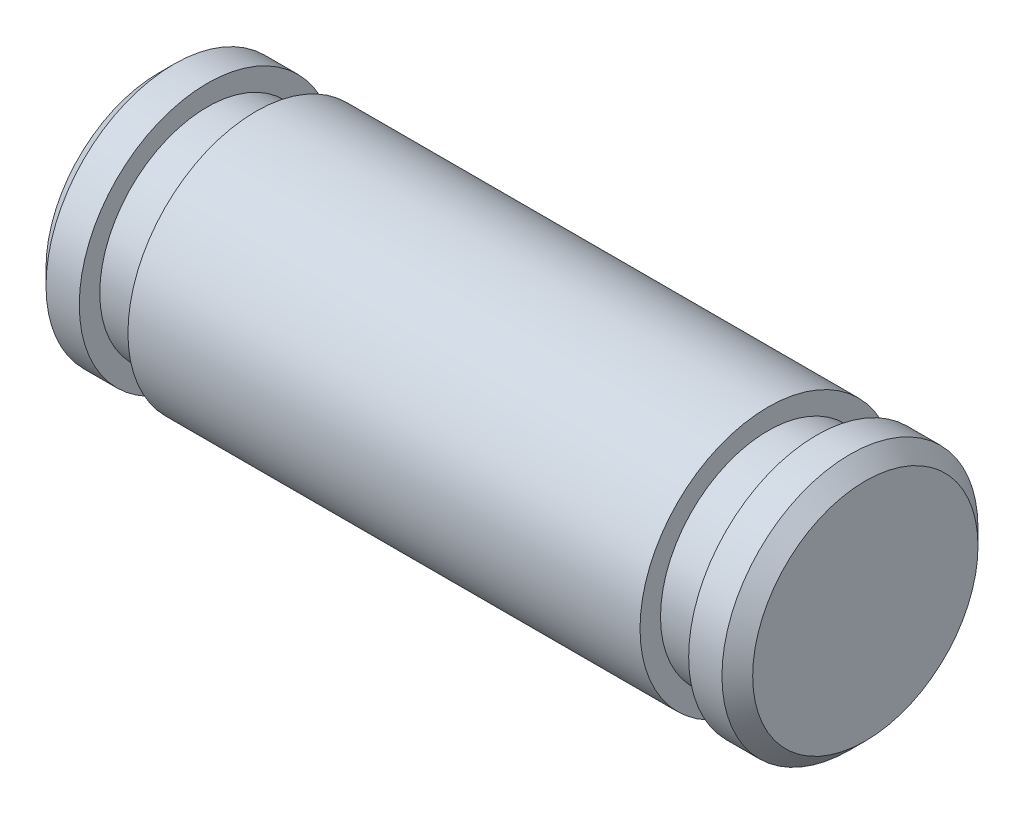
SolidWorks part; units mm, degrees
material "AISI 1045 Steel, cold drawn"
ref_plane "Front Plane" through (0, 0, 0) normal (0, 0, 1) x (1, 0, 0)
ref_plane "Top Plane" through (0, 0, 0) normal (0, 1, 0) x (1, 0, 0)
ref_plane "Right Plane" through (0, 0, 0) normal (1, 0, 0) x (0, 0, -1)
sketch "Sketch1" plane through (0, 0, 0) normal (0, 0, 1) x (1, 0, 0)
  line L0 (-8.763, 0) -> (-8.763, 2.794)
  line L1 (-8.763, 2.794) -> (-8.382, 3.175)
  line L2 (-8.382, 3.175) -> (-7.5565, 3.175)
  line L3 (-7.5565, 3.175) -> (-7.5565, 2.667)
  line L4 (-7.5565, 2.667) -> (-6.35, 2.667)
  line L5 (-6.35, 2.667) -> (-6.35, 3.175)
  line L6 (-6.35, 3.175) -> (6.35, 3.175)
  line L7 (6.35, 3.175) -> (6.35, 2.667)
  line L8 (6.35, 2.667) -> (7.5565, 2.667)
  line L9 (7.5565, 2.667) -> (7.5565, 3.175)
  line L10 (7.5565, 3.175) -> (8.382, 3.175)
  line L11 (8.382, 3.175) -> (8.763, 2.794)
  line L12 (8.763, 2.794) -> (8.763, 0)
  line L13 (8.763, 0) -> (-8.763, 0)
  line L14 (8.763, 0) -> (-8.763, 0) construction
revolve "Revolve1" add sketch "Sketch1" angle 360 about L14 reverse direction yes
ref_plane "Plane1" through (6.9533, 0, 0) normal (1, 0, 0) x (0, 0, -1)
ref_plane "Plane2" through (-6.9533, 0, 0) normal (1, 0, 0) x (0, 0, -1)
ref_plane "p1 XY" through (0, 0, 0) normal (1, 0, 0) x (0, 0, -1)
ref_plane "p1 XZ" through (0, 0, 0) normal (0, -1, 0) x (-1, 0, 0)
ref_plane "p1 YZ" through (0, 0, 3.175) normal (0, 0, -1) x (-1, 0, 0)
ref_axis "p1 X" through (0, 0, 80.9) along (0, 0, -1)
ref_axis "p1 Y" through (0, -50, 3.175) along (0, 1, 0)
ref_axis "p1 Z" through (80.9, 0, 3.175) along (-1, 0, 0)
sketch3d "p1"
  point P0 (0, 0, 3.175)
ref_plane "p2 XY" through (0, 0, 0) normal (1, 0, 0) x (0, 0, -1)
ref_plane "p2 XZ" through (0, 0, 0) normal (0, -1, 0) x (-1, 0, 0)
ref_plane "p2 YZ" through (0, 0, -3.175) normal (0, 0, -1) x (-1, 0, 0)
ref_axis "p2 X" through (0, 0, 80.9) along (0, 0, -1)
ref_axis "p2 Y" through (0, -50, -3.175) along (0, 1, 0)
ref_axis "p2 Z" through (80.9, 0, -3.175) along (-1, 0, 0)
sketch3d "p2"
  point P0 (0, 0, -3.175)
ref_plane "pin XY" through (0, 0, 0) normal (1, 0, 0) x (0, 0, -1)
ref_plane "pin XZ" through (0, 0, 0) normal (0, -1, 0) x (-1, 0, 0)
ref_plane "pin YZ" through (0, 0, 0) normal (0, 0, -1) x (-1, 0, 0)
ref_axis "pin X" through (0, 0, 80.9) along (0, 0, -1)
ref_axis "pin Y" through (0, -50, 0) along (0, 1, 0)
ref_axis "pin Z" through (80.9, 0, 0) along (-1, 0, 0)
sketch3d "pin"
  point P0 (0, 0, 0)
ref_plane "rr1 XY" through (6.9533, 0, 0) normal (1, 0, 0) x (0, 0, -1)
ref_plane "rr1 XZ" through (0, 0, 0) normal (0, -1, 0) x (-1, 0, 0)
ref_plane "rr1 YZ" through (0, 0, 0) normal (0, 0, -1) x (-1, 0, 0)
ref_axis "rr1 X" through (6.9533, 0, 80.9) along (0, 0, -1)
ref_axis "rr1 Y" through (6.9533, -50, 0) along (0, 1, 0)
ref_axis "rr1 Z" through (80.9, 0, 0) along (-1, 0, 0)
sketch3d "rr1"
  point P0 (6.9533, 0, 0)
ref_plane "rr2 XY" through (-6.9533, 0, 0) normal (1, 0, 0) x (0, 0, -1)
ref_plane "rr2 XZ" through (0, 0, 0) normal (0, -1, 0) x (-1, 0, 0)
ref_plane "rr2 YZ" through (0, 0, 0) normal (0, 0, -1) x (-1, 0, 0)
ref_axis "rr2 X" through (-6.9533, 0, 80.9) along (0, 0, -1)
ref_axis "rr2 Y" through (-6.9533, -50, 0) along (0, 1, 0)
ref_axis "rr2 Z" through (80.9, 0, 0) along (-1, 0, 0)
sketch3d "rr2"
  point P0 (-6.9533, 0, 0)
ref_plane "w21 XY" through (0, 0, 0) normal (0, 1, 0) x (1, 0, 0)
ref_plane "w21 XZ" through (0, 0, 0) normal (0, 0, 1) x (1, 0, 0)
ref_plane "w21 YZ" through (8.763, 0, 0) normal (1, 0, 0) x (0, 0, -1)
ref_axis "w21 X" through (-80.9, 0, 0) along (1, 0, 0)
ref_axis "w21 Y" through (8.763, 0, 50) along (0, 0, -1)
ref_axis "w21 Z" through (8.763, 50, 0) along (0, -1, 0)
sketch3d "w21"
  point P0 (8.763, 0, 0)
ref_plane "w22 XY" through (0, 0, 0) normal (0, 1, 0) x (1, 0, 0)
ref_plane "w22 XZ" through (0, 0, 0) normal (0, 0, 1) x (1, 0, 0)
ref_plane "w22 YZ" through (-8.763, 0, 0) normal (1, 0, 0) x (0, 0, -1)
ref_axis "w22 X" through (-80.9, 0, 0) along (1, 0, 0)
ref_axis "w22 Y" through (-8.763, 0, 50) along (0, 0, -1)
ref_axis "w22 Z" through (-8.763, 50, 0) along (0, -1, 0)
sketch3d "w22"
  point P0 (-8.763, 0, 0)
